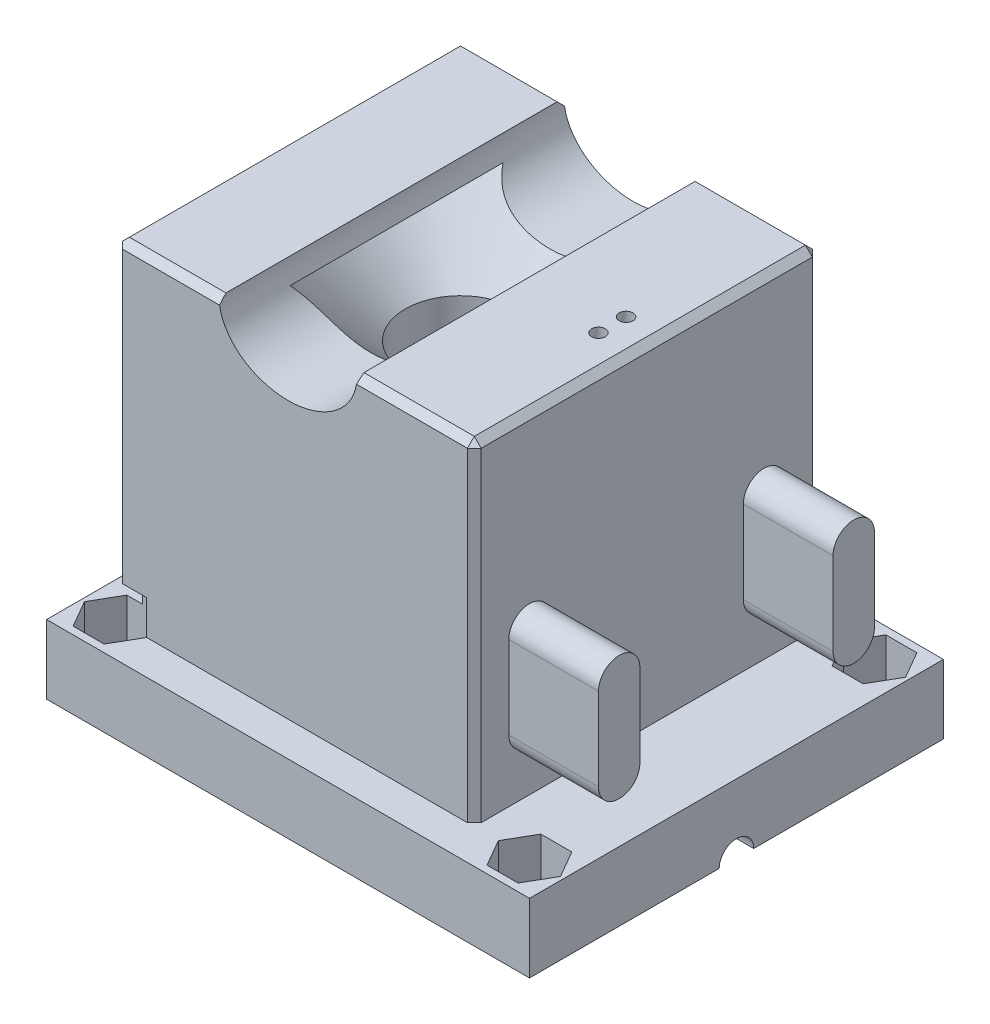
SolidWorks part; units mm, degrees
ref_plane "前视基准面" through (0, 0, 0) normal (0, 0, 1) x (1, 0, 0)
ref_plane "上视基准面" through (0, 0, 0) normal (0, 1, 0) x (1, 0, 0)
ref_plane "右视基准面" through (0, 0, 0) normal (1, 0, 0) x (0, 0, -1)
sketch "草图1" plane through (0, 0, 0) normal (0, 1, 0) x (1, 0, 0)
  line L1 (-35, 30) -> (35, 30)
  line L2 (-35, 30) -> (-35, -30)
  line L3 (-35, -30) -> (35, -30)
  line L4 (35, 30) -> (35, -30)
  line L5 (-35, 30) -> (35, -30) construction
  line L6 (-35, -30) -> (35, 30) construction
  point P0 (0, 0)
  dimension "D1" = 70
  dimension "D2" = 60
extrude "凸台-拉伸1" add sketch "草图1" along normal blind 58
sketch "草图2" plane through (0, 0, 0) normal (0, -1, 0) x (1, 0, 0)
  line L0 (-35, -30) -> (-35, 30) construction
  line L1 (-26, 21) -> (18, 21)
  line L2 (-26, 21) -> (-26, -21)
  line L3 (-26, -21) -> (18, -21)
  line L4 (18, 21) -> (18, -21)
  line L5 (-26, 21) -> (18, -21) construction
  line L6 (-26, -21) -> (18, 21) construction
  line L7 (35, 30) -> (35, -30) construction
  line L8 (-35, 30) -> (35, 30) construction
  line L9 (35, -30) -> (-35, -30) construction
  point P0 (-4, 0)
  dimension "D1" = 9
  dimension "D2" = 17
  dimension "D3" = 9
  dimension "D4" = 9
extrude "切除-拉伸1" cut sketch "草图2" against normal blind 35
sketch "草图3" plane through (0, 58, 0) normal (0, 1, 0) x (1, 0, 0)
  line L0 (35, -30) -> (35, 30) construction
  line L1 (-35, 30) -> (35, 30)
  line L2 (-35, 30) -> (-35, -30)
  line L3 (-35, -30) -> (35, -30)
  line L4 (35, 30) -> (35, -30)
  line L5 (-35, -30) -> (35, -30) construction
  line L7 (-30, 25) -> (22, 25)
  line L8 (-30, 25) -> (-30, -25)
  line L9 (-30, -25) -> (22, -25)
  line L10 (22, 25) -> (22, -25)
  dimension "D1" = 5
  dimension "D2" = 5
  dimension "D3" = 5
  dimension "D4" = 13
extrude "切除-拉伸3" cut sketch "草图3" against normal offset from surface (48 mm away) 10 up to face at (-4, 0, 0)
sketch "草图4" plane through (0, 58, 0) normal (0, 1, 0) x (1, 0, 0)
  line L0 (-30, -25) -> (-30, 25) construction
  line L2 (-30, 25) -> (22, 25) construction
  circle A0 centre (-5, 0) radius 8
  dimension "D1" = 16
  dimension "D3" = 25
  dimension "D2" = 25
extrude "切除-拉伸4" cut sketch "草图4" against normal through all
sketch "草图5" plane through (0, 0, 25) normal (0, 0, 1) x (1, 0, 0)
  line L0 (-30, 58) -> (22, 58) construction
  line L1 (-30, 10) -> (-30, 58) construction
  ellipse E0 centre (-5, 58) end of major axis (5, 58) minor radius 8
  dimension "D1" = 25
extrude "切除-拉伸5" cut sketch "草图5" against normal through all
ref_plane "基准面1" through (0, 45, 0) normal (0, -1, 0) x (-1, 0, 0)
sketch "草图6" plane through (0, 45, 0) normal (0, -1, 0) x (-1, 0, 0)
  circle A0 centre (5, 0) radius 8
extrude "切除-拉伸6" cut sketch "草图6" against normal blind 10 draft 45 draft outward yes
sketch "草图9" plane through (-30, 0, 0) normal (-1, 0, 0) x (0, 0, 1)
  line L0 (-14, 31) -> (-14, 19) construction
  line L1 (-11, 31) -> (-11, 19)
  line L2 (-17, 31) -> (-17, 19)
  line L3 (-25, 10) -> (-25, 58) construction
  line L4 (30, 10) -> (-30, 10) construction
  line L5 (0, 58) -> (0, 0) construction
  line L6 (-25, 58) -> (25, 58) construction
  line L7 (14, 31) -> (14, 19) construction
  line L8 (11, 31) -> (11, 19)
  line L9 (17, 31) -> (17, 19)
  arc A0 (-11, 31) -> (-17, 31) centre (-14, 31) ccw
  arc A1 (-17, 19) -> (-11, 19) centre (-14, 19) ccw
  arc A2 (11, 31) -> (17, 31) centre (14, 31) cw
  arc A3 (17, 19) -> (11, 19) centre (14, 19) cw
  point P2 (-14, 25)
  point P18 (14, 25)
  dimension "D3" = 3
  dimension "D1" = 8
  dimension "D2" = 15
  dimension "D4" = 12
extrude "凸台-拉伸2" add sketch "草图9" along normal blind 5
sketch "草图10" plane through (22, 0, 0) normal (1, 0, 0) x (0, 0, -1)
  line L0 (-17, 31) -> (-17, 19) construction
  line L1 (-14, 31) -> (-14, 19)
  line L2 (-20, 31) -> (-20, 19)
  line L3 (-25, 10) -> (-25, 58) construction
  line L4 (25, 10) -> (-25, 10) construction
  line L5 (0, 58) -> (0, 0) construction
  line L6 (-25, 58) -> (25, 58) construction
  line L7 (17, 31) -> (17, 19) construction
  line L8 (14, 31) -> (14, 19)
  line L9 (20, 31) -> (20, 19)
  arc A0 (-14, 31) -> (-20, 31) centre (-17, 31) ccw
  arc A1 (-20, 19) -> (-14, 19) centre (-17, 19) ccw
  arc A2 (14, 31) -> (20, 31) centre (17, 31) cw
  arc A3 (20, 19) -> (14, 19) centre (17, 19) cw
  point P2 (-17, 25)
  point P18 (17, 25)
  dimension "D4" = 3
  dimension "D1" = 8
  dimension "D2" = 12
  dimension "D3" = 15
extrude "凸台-拉伸3" add sketch "草图10" along normal blind 13
sketch "草图11" plane through (0, 35, 0) normal (0, -1, 0) x (1, 0, 0)
  line L0 (-26, -21) -> (18, -21) construction
  line L1 (18, 21) -> (-26, 21) construction
  line L2 (18, -21) -> (18, 21) construction
  circle A0 centre (17, -2) radius 1
  circle A2 centre (17, 2) radius 1
  dimension "D1" = 19
  dimension "D5" = 2
  dimension "D6" = 2
  dimension "D2" = 19
  dimension "D3" = 1
  dimension "D4" = 1
extrude "切除-拉伸7" cut sketch "草图11" against normal through all
sketch "草图13" plane through (35, 0, 0) normal (1, 0, 0) x (0, 0, -1)
  circle A0 centre (0, 0) radius 2.5
  dimension "D1" = 5
extrude "切除-拉伸8" cut sketch "草图13" against normal up to next
chamfer "倒角1" distance 1 angle 45 2 edges at (-30, 58, 0) (-22.5, 58, 25)
chamfer "倒角2" distance 1 angle 45 8 edges at (-30, 33.5, -25) (-30, 33.5, 25) (22, 34, -25) (22, 34, 25) (13.5, 58, 25) (22, 58, 0) (13.5, 58, -25) (-22, 58, -25)
sketch "草图14" plane through (0, 10, 0) normal (0, 1, 0) x (1, 0, 0)
  line L0 (25.5, 25.0103) -> (27.75, 28.9074)
  line L1 (-27.75, 21.1132) -> (-25.5, 25.0103)
  line L2 (-25.5, 25.0103) -> (-27.75, 28.9074)
  line L3 (-27.75, 28.9074) -> (-32.25, 28.9074)
  line L4 (-32.25, 28.9074) -> (-34.5, 25.0103)
  line L5 (-34.5, 25.0103) -> (-32.25, 21.1132)
  line L6 (-32.25, 21.1132) -> (-27.75, 21.1132)
  line L7 (-35, 30) -> (35, 30) construction
  line L8 (-35, -30) -> (-35, 30) construction
  line L9 (0, 30) -> (0, -30) construction
  line L10 (35, -30) -> (-35, -30) construction
  line L11 (-35, 0) -> (35, 0) construction
  line L12 (35, 30) -> (35, -30) construction
  line L13 (32.25, 28.9074) -> (34.5, 25.0103)
  line L14 (34.5, 25.0103) -> (32.25, 21.1132)
  line L15 (32.25, 21.1132) -> (27.75, 21.1132)
  line L16 (27.75, 21.1132) -> (25.5, 25.0103)
  line L17 (27.75, 28.9074) -> (32.25, 28.9074)
  line L18 (27.75, -28.9074) -> (32.25, -28.9074)
  line L19 (27.75, -21.1132) -> (25.5, -25.0103)
  line L20 (32.25, -21.1132) -> (27.75, -21.1132)
  line L21 (34.5, -25.0103) -> (32.25, -21.1132)
  line L22 (32.25, -28.9074) -> (34.5, -25.0103)
  line L23 (25.5, -25.0103) -> (27.75, -28.9074)
  line L24 (-32.25, -21.1132) -> (-27.75, -21.1132)
  line L25 (-34.5, -25.0103) -> (-32.25, -21.1132)
  line L26 (-32.25, -28.9074) -> (-34.5, -25.0103)
  line L27 (-27.75, -28.9074) -> (-32.25, -28.9074)
  line L28 (-25.5, -25.0103) -> (-27.75, -28.9074)
  line L29 (-27.75, -21.1132) -> (-25.5, -25.0103)
  circle A0 centre (-30, 25.0103) radius 3.8971 construction
  circle A1 centre (30, 25.0103) radius 3.8971 construction
  circle A2 centre (30, -25.0103) radius 3.8971 construction
  circle A3 centre (-30, -25.0103) radius 3.8971 construction
  dimension "D1" = 4.5
  dimension "D2" = 4.9897
  dimension "D3" = 5
extrude "切除-拉伸9" cut sketch "草图14" against normal blind 7 and the other way blind 5
sketch "草图15" plane through (0, 0, 0) normal (0, -1, 0) x (1, 0, 0)
  line L0 (-35, 30) -> (35, 30) construction
  line L1 (35, 30) -> (35, 2.5) construction
  line L5 (-35, -30) -> (-35, 30) construction
  line L6 (-35, 0) -> (35, 0) construction
  line L7 (35, -2.5) -> (35, 2.5) construction
  circle A0 centre (-30, 25) radius 2
  circle A1 centre (30, 25) radius 2
  circle A2 centre (30, -25) radius 2
  circle A3 centre (-30, -25) radius 2
  dimension "D1" = 4
  dimension "D4" = 4
  dimension "D2" = 5
  dimension "D3" = 5
  dimension "D5" = 5
  dimension "D6" = 5
extrude "切除-拉伸11" cut sketch "草图15" against normal up to next
